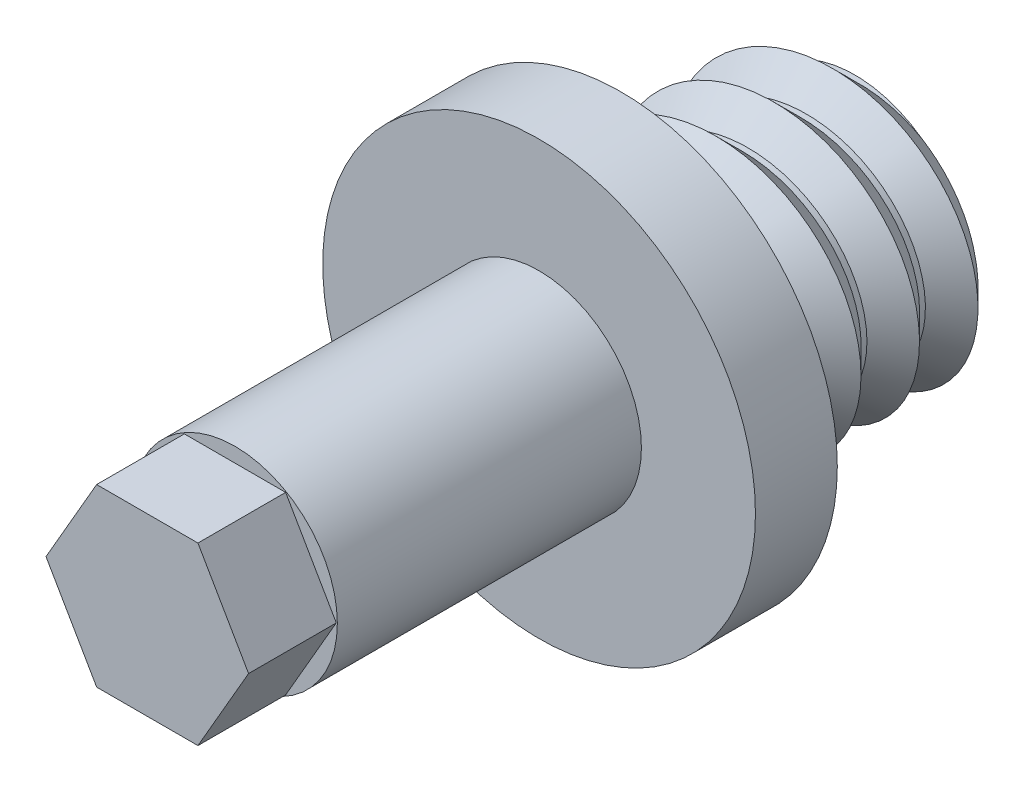
SolidWorks part; units mm, degrees
ref_plane "前视基准面" through (0, 0, 0) normal (0, 0, 1) x (1, 0, 0)
ref_plane "上视基准面" through (0, 0, 0) normal (0, 1, 0) x (1, 0, 0)
ref_plane "右视基准面" through (0, 0, 0) normal (1, 0, 0) x (0, 0, -1)
sketch "草图1" plane through (0, 0, 0) normal (0, 0, 1) x (1, 0, 0)
  circle A0 centre (0, 0) radius 7.4
  dimension "D1" = 14.8
extrude "凸台-拉伸1" add sketch "草图1" along normal blind 2.8
sketch "草图2" plane through (0, 0, 0) normal (0, 0, -1) x (-1, 0, 0)
  circle A0 centre (0, 0) radius 3.9
  dimension "D1" = 7.8
extrude "凸台-拉伸2" add sketch "草图2" along normal blind 8
sketch "草图3" plane through (0, 0, 0) normal (0, 0, -1) x (-1, 0, 0)
  circle A1 centre (0, 0) radius 3.9
  circle A2 centre (0, 0) radius 3.9
  dimension "D1" = 0
curve "螺旋线/涡状线1" pitch 2 height 7.5 turns 3.75
sketch "草图4" plane through (0, 0, 0) normal (1, 0, 0) x (0, 0, -1)
  line L0 (0, 3.9) -> (1.8, 3.9)
  line L1 (0, -3.9) -> (0, 3.9) construction
  line L2 (8, 3.9) -> (0, 3.9) construction
  line L5 (0, 3.9) -> (0.9, 4.8)
  line L6 (0.9, 4.8) -> (1.8, 3.9)
  spline S0 degree 3 poles (0, 3.9) (0.0414, 3.9) (0.1251, 3.6969) (0.25, 2.8295) (0.375, 1.5313) (0.5, 0) (0.625, -1.5313) (0.75, -2.8295) (0.875, -3.6969) (1, -4.0015) (1.125, -3.6969) (1.25, -2.8295) (1.4167, -1.0986) (1.5833, 1.0986) (1.75, 2.8295) (1.875, 3.6969) (2, 4.0015) (2.125, 3.6969) (2.25, 2.8295) (2.4167, 1.0986) (2.5833, -1.0986) (2.75, -2.8295) (2.875, -3.6969) (3, -4.0015) (3.125, -3.6969) (3.25, -2.8295) (3.4167, -1.0986) (3.5833, 1.0986) (3.75, 2.8295) (3.875, 3.6969) (4, 4.0015) (4.125, 3.6969) (4.25, 2.8295) (4.4167, 1.0986) (4.5833, -1.0986) (4.75, -2.8295) (4.875, -3.6969) (5, -4.0015) (5.125, -3.6969) (5.25, -2.8295) (5.4167, -1.0986) (5.5833, 1.0986) (5.75, 2.8295) (5.875, 3.6969) (6, 4.0015) (6.125, 3.6969) (6.25, 2.8295) (6.4167, 1.0986) (6.5833, -1.0986) (6.75, -2.8295) (6.875, -3.6969) (7, -4.0015) (7.125, -3.697) (7.25, -2.8291) (7.3749, -1.5328) (7.4586, -0.5073) (7.5, 0) knots 0 0 0 0 0.016667 0.033333 0.05 0.066667 0.083333 0.1 0.116667 0.133333 0.15 0.166667 0.183333 0.216667 0.233333 0.25 0.266667 0.283333 0.3 0.316667 0.35 0.366667 0.383333 0.4 0.416667 0.433333 0.45 0.483333 0.5 0.516667 0.533333 0.55 0.566667 0.583333 0.616667 0.633333 0.65 0.666667 0.683333 0.7 0.716667 0.75 0.766667 0.783333 0.8 0.816667 0.833333 0.85 0.883333 0.9 0.916667 0.933333 0.95 0.966667 0.983333 1 1 1 1 construction
  dimension "D1" = 1.8
sweep "扫描1" add profiles "草图4" path "螺旋线/涡状线1"
sketch "草图5" plane through (0, 0, -8) normal (0, 0, -1) x (-1, 0, 0)
  circle A0 centre (0, 0) radius 6.214
extrude "切除-拉伸1" cut sketch "草图5" along normal blind 5
sketch "草图6" plane through (0, 0, 2.8) normal (0, 0, 1) x (1, 0, 0)
  circle A0 centre (0, 0) radius 3.5
  dimension "D1" = 7
extrude "凸台-拉伸3" add sketch "草图6" along normal blind 10.4
sketch "草图7" plane through (0, 0, 13.2) normal (0, 0, 1) x (1, 0, 0)
  line L1 (3.4641, 0) -> (1.7321, 3)
  line L2 (1.7321, 3) -> (-1.7321, 3)
  line L3 (-1.7321, 3) -> (-3.4641, 0)
  line L4 (-3.4641, 0) -> (-1.7321, -3)
  line L5 (-1.7321, -3) -> (1.7321, -3)
  line L6 (1.7321, -3) -> (3.4641, 0)
  circle A0 centre (0, 0) radius 3 construction
  dimension "D1" = 6
extrude "凸台-拉伸4" add sketch "草图7" along normal blind 3
